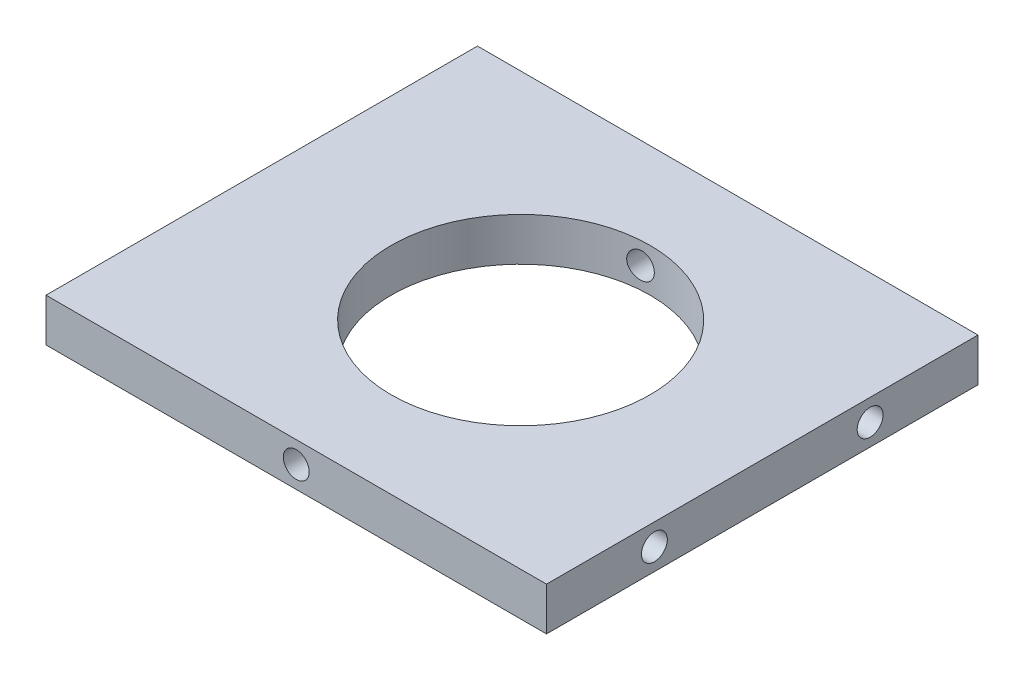
SolidWorks part; units mm, degrees
ref_plane "Plan de face" through (0, 0, 0) normal (0, 0, 1) x (1, 0, 0)
ref_plane "Plan de dessus" through (0, 0, 0) normal (0, 1, 0) x (1, 0, 0)
ref_plane "Plan de droite" through (0, 0, 0) normal (1, 0, 0) x (0, 0, -1)
sketch "Esquisse1" plane through (0, 0, 0) normal (0, 0, 1) x (1, 0, 0)
  line L0 (-5.5, -47.5) -> (52.5, -47.5) construction
  line L5 (-5.5, -45) -> (52.5, -45)
  line L6 (-5.5, -45) -> (-5.5, -50)
  line L7 (-5.5, -50) -> (52.5, -50)
  line L8 (52.5, -45) -> (52.5, -50)
  line L9 (23.5, -45) -> (23.5, -50) construction
  dimension "D1" = 5
  dimension "D2" = 58
extrude "Boss.-Extru.1" add sketch "Esquisse1" along normal blind 50 contours L5 | L7 L8 L5 L6
sketch "Esquisse2" plane through (0, -45, 0) normal (0, 1, 0) x (-1, 0, 0)
  line L0 (5.5, 50) -> (-52.5, 50) construction
  line L7 (-52.5, 50) -> (-52.5, 0) construction
  circle A0 centre (-24.5, 25) radius 15
  dimension "D10" = 28
  dimension "D11" = 25
extrude "Enlèv. mat.-Extru.1" cut sketch "Esquisse2" against normal through all
sketch "Esquisse3" plane through (-5.5, 0, 0) normal (-1, 0, 0) x (0, 0, 1)
  line L0 (50, -50) -> (0, -50) construction
  line L1 (0, -45) -> (0, -50) construction
  line L2 (50, -45) -> (50, -50) construction
  circle A0 centre (12.5, -47.5) radius 1.5
  circle A1 centre (37.5, -47.5) radius 1.5
  dimension "D1" = 2.5
  dimension "D2" = 2.5
  dimension "D3" = 12.5
  dimension "D4" = 12.5
extrude "Enlèv. mat.-Extru.2" cut sketch "Esquisse3" against normal blind 10
sketch "Esquisse4" plane through (52.5, 0, 0) normal (1, 0, 0) x (0, 0, -1)
  line L0 (-50, -50) -> (0, -50) construction
  line L1 (-50, -45) -> (-50, -50) construction
  line L2 (0, -45) -> (0, -50) construction
  circle A0 centre (-37.5, -47.5) radius 1.5
  circle A1 centre (-12.5, -47.5) radius 1.5
  dimension "D1" = 2.5
  dimension "D2" = 2.5
  dimension "D3" = 12.5
  dimension "D4" = 12.5
extrude "Enlèv. mat.-Extru.3" cut sketch "Esquisse4" against normal blind 10
sketch "Esquisse5" plane through (0, 0, 50) normal (0, 0, 1) x (1, 0, 0)
  line L0 (-5.5, -45) -> (-5.5, -50) construction
  line L1 (-5.5, -50) -> (52.5, -50) construction
  circle A0 centre (23.5, -47.5) radius 1.5
  dimension "D1" = 29
  dimension "D2" = 2.5
extrude "Enlèv. mat.-Extru.4" cut sketch "Esquisse5" against normal through all
